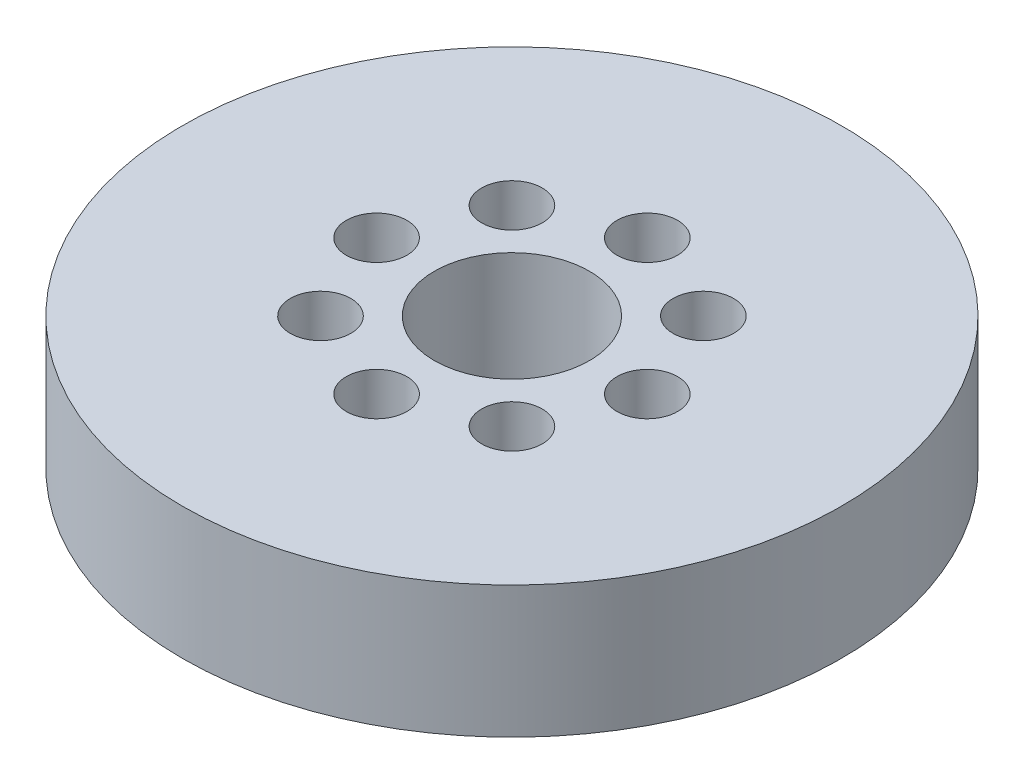
SolidWorks part; units mm, degrees
ref_plane "Front Plane" through (0, 0, 0) normal (0, 0, 1) x (1, 0, 0)
ref_plane "Top Plane" through (0, 0, 0) normal (0, 1, 0) x (1, 0, 0)
ref_plane "Right Plane" through (0, 0, 0) normal (1, 0, 0) x (0, 0, -1)
sketch "Sketch1" plane through (0, 0, 0) normal (0, 1, 0) x (1, 0, 0)
  circle A0 centre (0, 0) radius 42.5
  dimension "FLANGE_OD" = 85
extrude "Boss-Extrude1" add sketch "Sketch1" along normal blind 17
sketch "Sketch2" plane through (0, 0, 0) normal (0, 1, 0) x (1, 0, 0)
  circle A0 centre (0, 0) radius 10
  dimension "BORE_D" = 20
extrude "Cut-Extrude1" cut sketch "Sketch2" along normal through all
sketch "Sketch3" plane through (0, 17, 0) normal (0, 1, 0) x (1, 0, 0)
  circle A0 centre (0, 0) radius 17.4541 construction
  circle A1 centre (-17.4541, 0) radius 3.9073
  dimension "BOLT_D" = 7.8146
  dimension "BOLT_PCD" = 34.9082
extrude "Cut-Extrude2" cut sketch "Sketch3" against normal blind 11.9591
pattern_circular "CirPattern1" count 8 over 360 about axis through (0, 0, 0) along (0, 1, 0) of "Cut-Extrude2"
